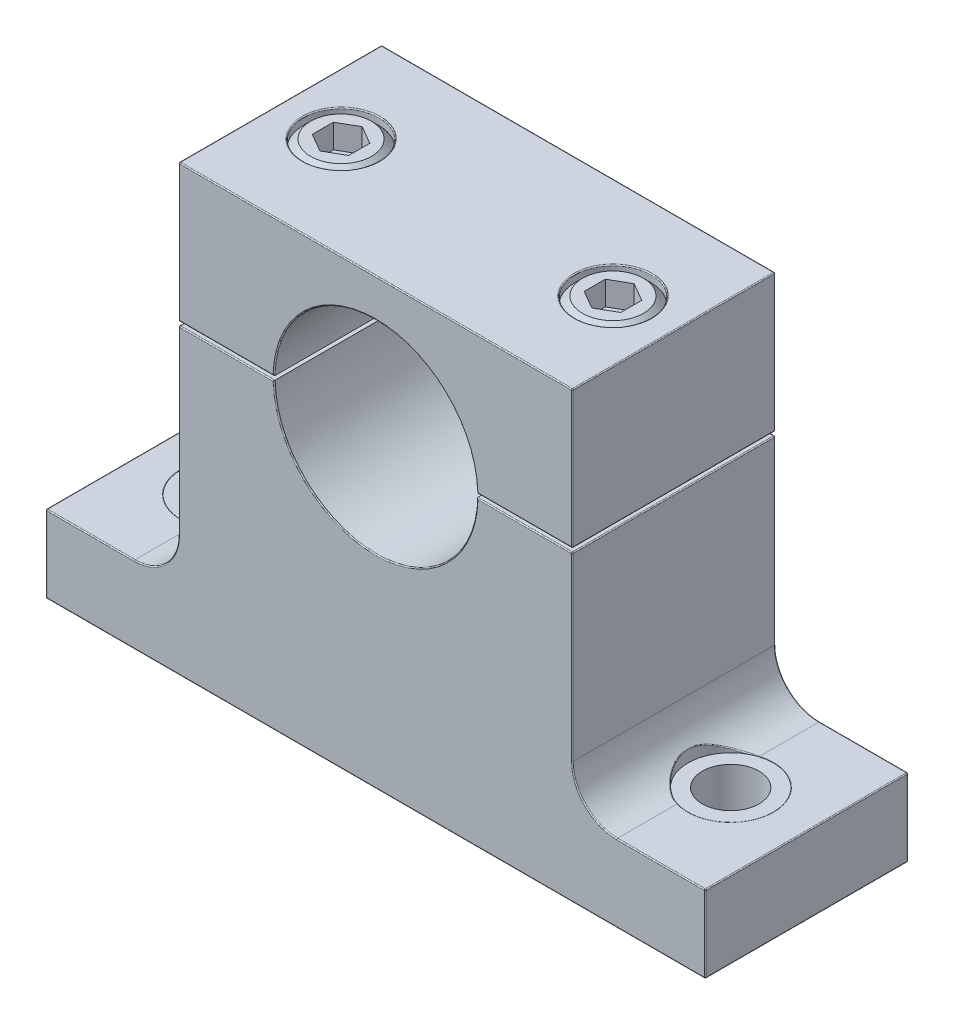
SolidWorks part; units mm, degrees
note: '?' marks a value the reader was unsure of.
material "6061-T6 (SS)"
ref_plane "Front Plane" through (0, 0, 0) normal (0, 0, 1) x (1, 0, 0)
ref_plane "Top Plane" through (0, 0, 0) normal (0, 1, 0) x (1, 0, 0)
ref_plane "Right Plane" through (0, 0, 0) normal (1, 0, 0) x (0, 0, -1)
sketch "Sketch1" plane through (0, 0, 0) normal (0, 0, 1) x (1, 0, 0)
  line L0 (0, 17.4625) -> (0, -38.1) construction
  line L1 (41.275, -38.1) -> (-41.275, -38.1) construction
  line L2 (-24.638, 17.4625) -> (24.638, 17.4625) construction
  line L3 (0, 0.25) -> (0, -0.25) construction
  line L4 (-17.018, 0) -> (17.018, 0) construction
  line L5 (-31.75, -28.448) -> (31.75, -28.448) construction
  line L6 (-17.018, 17.4625) -> (-17.018, -38.1) construction
  line L7 (-21.7805, 17.4625) -> (-12.2555, 17.4625) construction
  line L8 (-20.193, -38.1) -> (-13.843, -38.1) construction
  line L9 (-35.306, -28.448) -> (-28.194, -28.448) construction
  line L10 (-37.084, -28.448) -> (-26.416, -28.448) construction
  circle A0 centre (0, 0) radius 12.7 construction
  point P7 (0, 0)
  point P8 (0, -38.1)
  point P11 (0, -28.448)
  point P14 (0, 17.4625)
  point P15 (0, 0)
  point P20 (0, -28.448)
  point P23 (-17.018, 11.1125)
  point P26 (-17.018, 17.4625)
  point P27 (-17.018, -38.1)
  point P30 (-31.75, -28.448)
  point P35 (-31.75, -28.448)
  dimension "D1" = 0.5
  dimension "D3" = 6.35
  dimension "D4" = 10.668
sketch "Sketch2" plane through (0, 0, 0) normal (0, 0, 1) x (1, 0, 0)
  line L0 (-24.638, 17.4625) -> (24.638, 17.4625)
  line L1 (41.275, -38.1) -> (-41.275, -38.1) construction
  line L2 (41.275, -38.1) -> (-41.275, -38.1)
  line L3 (-41.275, -38.1) -> (-41.275, -28.448)
  line L4 (-41.275, -28.448) -> (-30.1943, -28.448)
  line L5 (-24.638, -22.8918) -> (-24.638, -0.25)
  line L6 (24.638, 17.4625) -> (24.638, 0.25)
  line L7 (30.1943, -28.448) -> (41.275, -28.448)
  line L8 (41.275, -28.448) -> (41.275, -38.1)
  line L9 (-24.638, 0.25) -> (-12.6975, 0.25)
  line L10 (-24.638, -0.25) -> (-12.6975, -0.25)
  line L11 (-24.638, 0.25) -> (-24.638, 17.4625)
  line L12 (24.638, -0.25) -> (24.638, -22.8918)
  line L13 (12.6975, 0.25) -> (24.638, 0.25)
  line L14 (12.6975, -0.25) -> (24.638, -0.25)
  circle A0 centre (0, 0) radius 12.7 construction
  arc A1 (-12.6975, -0.25) -> (12.6975, -0.25) centre (0, 0) ccw
  arc A2 (12.6975, 0.25) -> (-12.6975, 0.25) centre (0, 0) ccw
  arc A3 (24.638, -22.8918) -> (30.1943, -28.448) centre (30.1943, -22.8918) ccw
  arc A4 (-30.1943, -28.448) -> (-24.638, -22.8918) centre (-30.1943, -22.8918) ccw
  dimension "D1" = 5.5562
extrude "Boss-Extrude1" add sketch "Sketch2" along normal mid plane 25.4
sketch "Sketch3" plane through (0, -28.448, 0) normal (0, 1, 0) x (1, 0, 0)
  line L0 (41.275, 0) -> (-41.275, 0) construction
  line L1 (-17.018, 0) -> (17.018, 0) construction
  circle A0 centre (-17.018, 0) radius 4.7625
  circle A1 centre (17.018, 0) radius 4.7625
  circle A2 centre (-31.75, 0) radius 3.556
  circle A3 centre (31.75, 0) radius 3.556
  circle A4 centre (-31.75, 0) radius 5.334 construction
  circle A5 centre (31.75, 0) radius 5.334 construction
  circle A6 centre (-17.018, 0) radius 4.7625 construction
  circle A9 centre (17.018, 0) radius 4.7625 construction
  point P6 (0, 0)
  point P16 (0, 0)
sketch "Sketch4" plane through (0, -28.448, 0) normal (0, 1, 0) x (1, 0, 0)
  circle A0 centre (-31.75, 0) radius 3.556 construction
  circle A1 centre (31.75, 0) radius 3.556 construction
  circle A2 centre (-31.75, 0) radius 3.556
  circle A3 centre (31.75, 0) radius 3.556
  point P0 (-31.75, 0)
extrude "Cut-Extrude1" cut sketch "Sketch4" against normal through all
sketch "Sketch5" plane through (0, -28.448, 0) normal (0, 1, 0) x (1, 0, 0)
  circle A0 centre (31.75, 0) radius 5.334 construction
  circle A1 centre (-31.75, 0) radius 5.334 construction
  circle A2 centre (31.75, 0) radius 5.334
  circle A3 centre (-31.75, 0) radius 5.334
extrude "Cut-Extrude2" cut sketch "Sketch5" against normal blind 0.02 and the other way through all
sketch "Sketch6" plane through (0, 17.4625, 0) normal (0, 1, 0) x (1, 0, 0)
  circle A0 centre (17.018, 0) radius 4.7625 construction
  circle A1 centre (-17.018, 0) radius 4.7625 construction
  circle A2 centre (17.018, 0) radius 4.7625
  circle A3 centre (-17.018, 0) radius 4.7625
extrude "Cut-Extrude3" cut sketch "Sketch6" against normal up to vertex (6.35 mm away) up to point (-17.018, 11.1125, 0)
sketch "Sketch8" plane through (0, 11.1125, 0) normal (0, 1, 0) x (1, 0, 0)
  circle A2 centre (17.018, 0) radius 3.175
  circle A3 centre (-17.018, 0) radius 3.175
extrude "Cut-Extrude4" cut sketch "Sketch8" against normal through all
sketch "Sketch10" plane through (0, 0, 0) normal (0, 0, 1) x (1, 0, 0)
  line L4 (-17.018, 17.4625) -> (-12.2555, 17.4625)
  line L5 (-12.2555, 17.4625) -> (-12.2555, 11.1125)
  line L6 (-12.2555, 11.1125) -> (-13.843, 11.1125)
  line L7 (-13.843, 11.1125) -> (-13.843, -38.1)
  line L10 (-13.843, -38.1) -> (-17.018, -38.1)
  line L11 (-17.018, -38.1) -> (-17.018, 17.4625)
revolve "Revolve1" add sketch "Sketch10" angle 360 about L11
sketch "Sketch11" plane through (0, 17.4625, 0) normal (0, 1, 0) x (1, 0, 0)
  line L1 (-17.018, 2.6396) -> (-19.304, 1.3198)
  line L2 (-19.304, 1.3198) -> (-19.304, -1.3198)
  line L3 (-19.304, -1.3198) -> (-17.018, -2.6396)
  line L4 (-17.018, -2.6396) -> (-14.732, -1.3198)
  line L5 (-14.732, -1.3198) -> (-14.732, 1.3198)
  line L6 (-14.732, 1.3198) -> (-17.018, 2.6396)
  circle A0 centre (-17.018, 0) radius 2.286 construction
  circle A1 centre (-17.018, 0) radius 4.7625 construction
  circle A2 centre (-17.018, 0) radius 4.7625 construction
  dimension "D1" = 9.525
  dimension "D2" = 4.572
extrude "Cut-Extrude5" cut sketch "Sketch11" against normal blind 3
chamfer "Chamfer1" distance 0.9525 angle 45 1 edges at (-12.2555, 17.4625, 0)
mirror "Mirror1" about plane through (0, 0, 0) normal (1, 0, 0) of bodies 112
fillet "Fillet1" radius 0.127 36 edges at (26.4412, -26.9889, -0.5175) (-26.4412, -26.9889, 0.5175) (28.194, -38.1, 0) (-35.306, -38.1, 0) (-20.193, -38.1, 0) (13.843, -38.1, 0) (41.275, -38.1, 0) (41.275, -28.448, 0) (24.638, -0.25, 0) (-24.638, -0.25, 0) (-41.275, -28.448, 0) (-41.275, -38.1, 0) (35.7346, -28.448, -12.7) (26.2654, -26.8206, -12.7) (24.638, -11.5709, -12.7) (18.6678, -0.25, -12.7) (0, -12.7, -12.7) (-18.6678, -0.25, -12.7) (-24.638, -11.5709, -12.7) (-26.2654, -26.8206, -12.7) (-35.7346, -28.448, -12.7) (-41.275, -33.274, -12.7) (0, -38.1, -12.7) (41.275, -33.274, -12.7) (0, -38.1, 12.7) (-41.275, -33.274, 12.7) (-35.7346, -28.448, 12.7) (-26.2654, -26.8206, 12.7) (-24.638, -11.5709, 12.7) (-18.6678, -0.25, 12.7) (0, -12.7, 12.7) (18.6678, -0.25, 12.7) (24.638, -11.5709, 12.7) (26.2654, -26.8206, 12.7) (35.7346, -28.448, 12.7) (41.275, -33.274, 12.7)
fillet "Fillet2" radius 0.127 18 edges at (24.638, 0.25, 0) (-18.6678, 0.25, -12.7) (0, 12.7, -12.7) (18.6678, 0.25, -12.7) (24.638, 8.8563, -12.7) (-24.638, 0.25, 0) (-24.638, 8.8563, -12.7) (24.638, 17.4625, 0) (-24.638, 17.4625, 0) (0, 17.4625, -12.7) (-21.7805, 17.4625, 0) (12.2555, 17.4625, 0) (0, 17.4625, 12.7) (24.638, 8.8563, 12.7) (18.6678, 0.25, 12.7) (0, 12.7, 12.7) (-18.6678, 0.25, 12.7) (-24.638, 8.8563, 12.7)
ref_plane "Contact Plane 1" through (0, -38.1, 0) normal (0, -1, 0) x (-1, 0, 0)
ref_axis "Center Axis 1" through (0, 0, 12.573) along (0, 0, -1)?
equation "\"D3@Sketch1\"=\"G@Sketch1\""
equation "\"D4@Sketch1\"=\"K@Sketch1\"*1.5"
equation "\"D2@Sketch11\"=\"D1@Sketch11\"*.48"
equation "\"D1@Sketch2\"=\"Height@Sketch1\"*.1"
equation "\"D1@Chamfer1\"=\"Screw Head Dia@Sketch1\"*.1"
